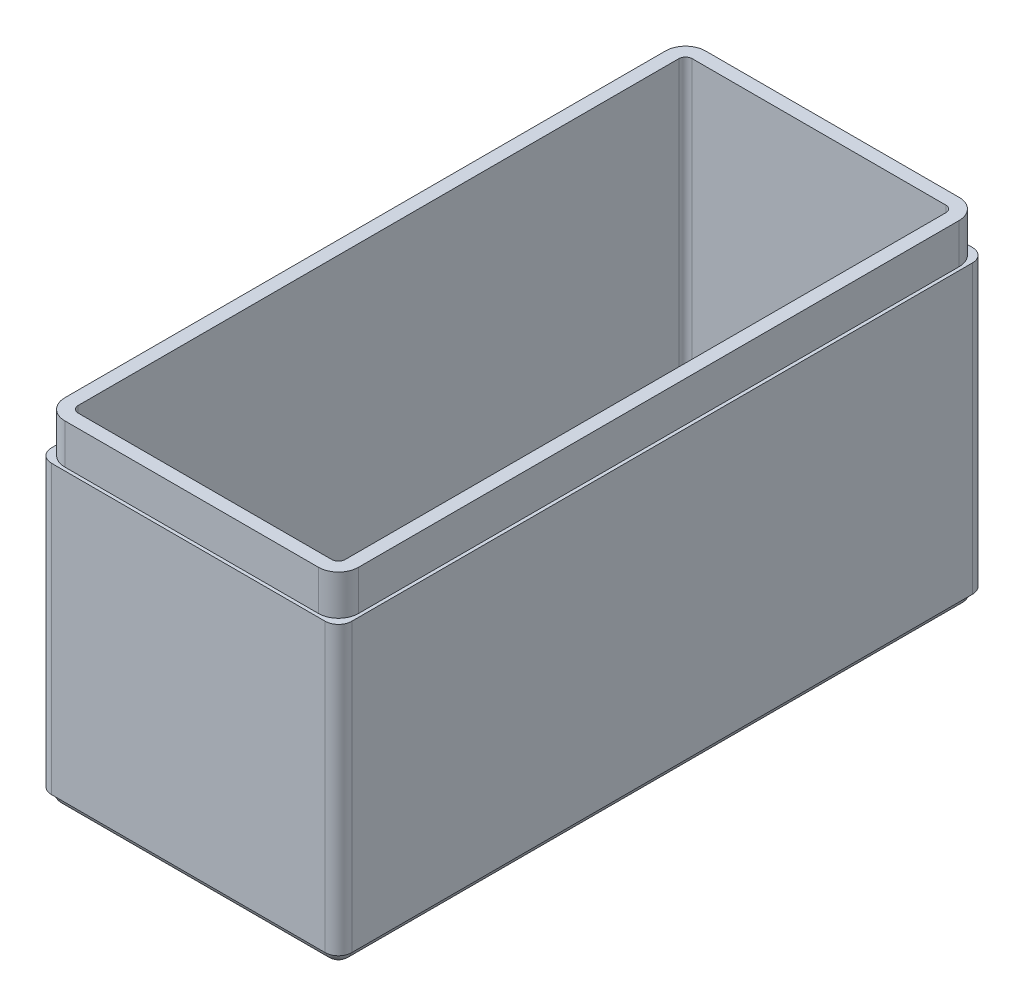
SolidWorks part; units mm, degrees
material "ABS"
ref_plane "Front Plane" through (0, 0, 0) normal (0, 0, 1) x (1, 0, 0)
ref_plane "Top Plane" through (0, 0, 0) normal (0, 1, 0) x (1, 0, 0)
ref_plane "Right Plane" through (0, 0, 0) normal (1, 0, 0) x (0, 0, -1)
sketch "Sketch1" plane through (0, 0, 0) normal (0, 1, 0) x (1, 0, 0)
  line L1 (-22.5, 48.5) -> (22.5, 48.5)
  line L2 (-22.5, 48.5) -> (-22.5, -48.5)
  line L3 (-22.5, -48.5) -> (22.5, -48.5)
  line L4 (22.5, 48.5) -> (22.5, -48.5)
  line L5 (-22.5, 48.5) -> (22.5, -48.5) construction
  line L6 (-22.5, -48.5) -> (22.5, 48.5) construction
  point P0 (0, 0)
  dimension "D1" = 45
  dimension "D2" = 97
extrude "Boss-Extrude1" add sketch "Sketch1" along normal mid plane 45
sketch "Sketch2" plane through (0, 22.5, 0) normal (0, 1, 0) x (1, 0, 0)
  line L0 (-22.5, -48.5) -> (22.5, -48.5) construction
  line L1 (-22, 48) -> (22, 48)
  line L2 (-22, 48) -> (-22, -48)
  line L3 (-22, -48) -> (22, -48)
  line L4 (22, 48) -> (22, -48)
  line L5 (-22, 48) -> (22, -48) construction
  line L6 (-22, -48) -> (22, 48) construction
  line L7 (-22.5, 48.5) -> (-22.5, -48.5) construction
  point P0 (0, 0)
  dimension "D1" = 0.5
  dimension "D2" = 0.5
extrude "Boss-Extrude2" add sketch "Sketch2" along normal blind 6
sketch "Sketch3" plane through (0, -22.5, 0) normal (0, -1, 0) x (1, 0, 0)
  line L1 (-22, 48) -> (22, 48)
  line L2 (-22, 48) -> (-22, -48)
  line L3 (-22, -48) -> (22, -48)
  line L4 (22.5, -48.5) -> (22.5, 48.5)
  line L5 (22.5, 48.5) -> (-22.5, 48.5)
  line L6 (-22.5, 48.5) -> (-22.5, -48.5)
  line L7 (-22.5, -48.5) -> (22.5, -48.5)
  line L8 (22.5, -48.5) -> (22.5, 48.5)
  line L9 (22.5, 48.5) -> (-22.5, 48.5)
  line L10 (-22.5, 48.5) -> (-22.5, -48.5)
  line L11 (-22.5, -48.5) -> (22.5, -48.5)
  line L12 (22, 48) -> (22, -48)
  line L13 (-22, 48) -> (22, -48) construction
  line L14 (-22, -48) -> (22, 48) construction
  point P2 (0, 0)
  dimension "D2" = 0.5
  dimension "D3" = 0.5
  dimension "D4" = 44
  dimension "D5" = 96
  dimension "D1" = 0
extrude "Cut-Extrude1" cut sketch "Sketch3" against normal blind 2
fillet "Fillet1" radius 2 4 edges at (0, -22.5, -48) (-22, -22.5, 0) (0, -22.5, 48) (22, -22.5, 0)
fillet "Fillet4" radius 3 4 edges at (-22, 25.5, 48) (22, 25.5, 48) (22, 25.5, -48) (-22, 25.5, -48)
fillet "Fillet5" radius 2 4 edges at (-22.5, 1, 48.5) (22.5, 1, 48.5) (-22.5, 1, -48.5) (22.5, 1, -48.5)
shell "Shell2" thickness 2 removed face at (0, 28.5, 0)
sketch "Sketch4" plane through (0, 20.5, 0) normal (0, -1, 0) x (1, 0, 0)
  line L4 (-20.5, 46.5) -> (-20.5, -46.5)
  line L5 (-20.5, -46.5) -> (20.5, -46.5)
  line L6 (20.5, -46.5) -> (20.5, 46.5)
  line L7 (20.5, 46.5) -> (-20.5, 46.5)
  line L8 (-20.5, 46.5) -> (-20.5, -46.5)
  line L9 (-20.5, -46.5) -> (20.5, -46.5)
  line L10 (20.5, -46.5) -> (20.5, 46.5)
  line L11 (20.5, 46.5) -> (-20.5, 46.5)
  line L12 (19, -46) -> (-19, -46) construction
  line L13 (-20, -45) -> (-20, 45) construction
  line L14 (-19, 46) -> (19, 46) construction
  line L15 (20, 45) -> (20, -45) construction
  line L16 (19, -46) -> (-19, -46)
  line L17 (-20, -45) -> (-20, 45)
  line L18 (-19, 46) -> (19, 46)
  line L19 (20, 45) -> (20, -45)
  arc A0 (19, -46) -> (20, -45) centre (19, -45) ccw construction
  arc A1 (-20, -45) -> (-19, -46) centre (-19, -45) ccw construction
  arc A2 (-19, 46) -> (-20, 45) centre (-19, 45) ccw construction
  arc A3 (20, 45) -> (19, 46) centre (19, 45) ccw construction
  arc A4 (19, -46) -> (20, -45) centre (19, -45) ccw
  arc A5 (-20, -45) -> (-19, -46) centre (-19, -45) ccw
  arc A6 (-19, 46) -> (-20, 45) centre (-19, 45) ccw
  arc A7 (20, 45) -> (19, 46) centre (19, 45) ccw
  dimension "D1" = 0
extrude "Boss-Extrude3" add sketch "Sketch4" along normal up to surface (41 mm away) up to face at (0, -20.5, 0)
